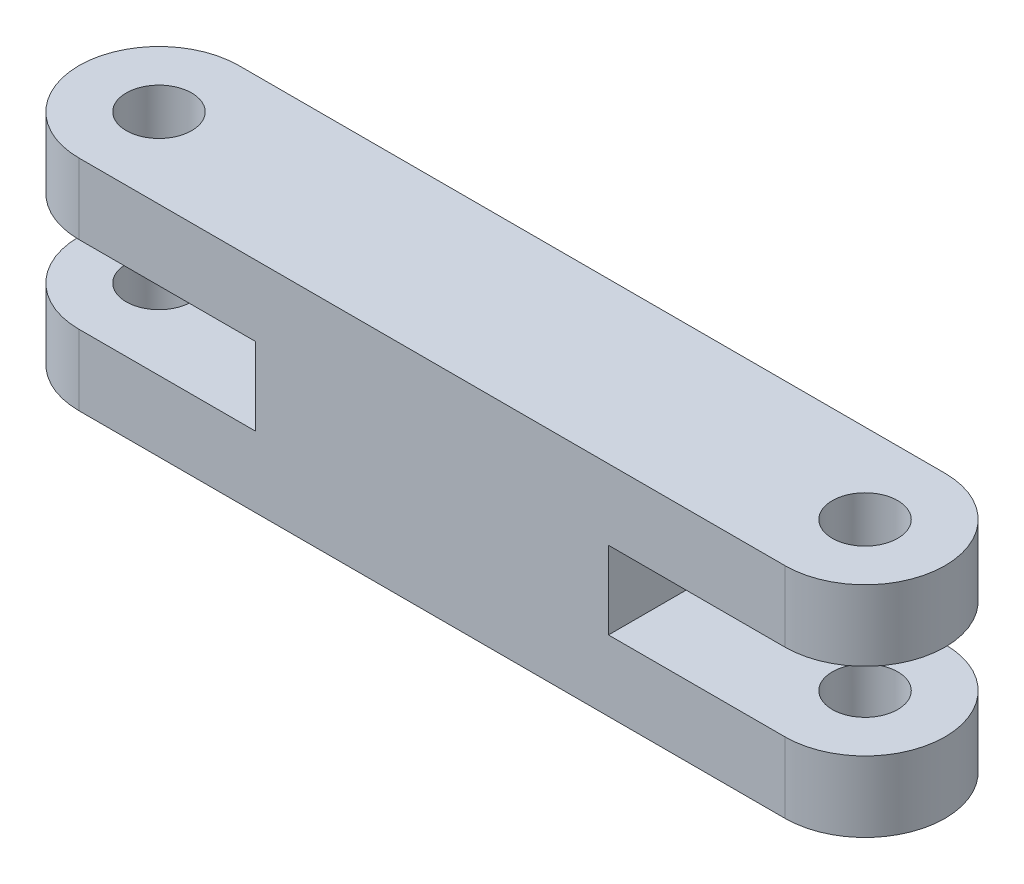
SolidWorks part; units mm, degrees
ref_plane "Front Plane" through (0, 0, 0) normal (0, 0, 1) x (1, 0, 0)
ref_plane "Top Plane" through (0, 0, 0) normal (0, 1, 0) x (1, 0, 0)
ref_plane "Right Plane" through (0, 0, 0) normal (1, 0, 0) x (0, 0, -1)
sketch "Sketch1" plane through (0, 0, 0) normal (0, 0, 1) x (1, 0, 0)
  line L0 (3.4, -9.3) -> (3.4, 0)
  line L1 (3.4, 0) -> (33.4, 0)
  line L2 (33.4, 0) -> (33.4, -9.3)
  line L3 (33.4, -9.3) -> (3.4, -9.3)
  point P2 (0, 0)
extrude "Boss-Extrude2" add sketch "Sketch1" along normal blind 3.4 and the other way blind 3.4
sketch "Sketch3" plane through (0, 0, 3.4) normal (0, 0, 1) x (1, 0, 0)
  line L0 (3.4, -3) -> (3.4, -6.3)
  line L1 (3.4, -3) -> (10.9, -3)
  line L2 (3.4, -6.3) -> (10.9, -6.3)
  line L3 (10.9, -3) -> (10.9, -6.3)
extrude "Cut-Extrude1" cut sketch "Sketch3" against normal blind 6.8 contours L0 L2 L3 L1
sketch "Sketch4" plane through (0, 0, 3.4) normal (0, 0, 1) x (1, 0, 0)
  line L0 (33.4, -3) -> (33.4, -6.3)
  line L1 (33.4, -3) -> (25.9, -3)
  line L2 (33.4, -6.3) -> (25.9, -6.3)
  line L3 (25.9, -3) -> (25.9, -6.3)
extrude "Cut-Extrude2" cut sketch "Sketch4" against normal blind 6.8 contours L0 L2 L3 L1
sketch "Sketch5" plane through (0, 0, 0) normal (0, 1, 0) x (1, 0, 0)
  line L0 (3.4, 3.4) -> (3.4, -3.4)
  arc A0 (3.4, 3.4) -> (3.4, -3.4) centre (3.4, 0) ccw
extrude "Boss-Extrude3" add sketch "Sketch5" against normal up to vertex (3 mm away) up to point (3.4, -3, -3.4)
sketch "Sketch6" plane through (0, 0, 0) normal (0, 1, 0) x (1, 0, 0)
  line L0 (33.4, 3.4) -> (33.4, -3.4)
  arc A0 (33.4, 3.4) -> (33.4, -3.4) centre (33.4, 0) cw
extrude "Boss-Extrude4" add sketch "Sketch6" against normal up to vertex (3 mm away) up to point (33.4, -3, -3.4)
sketch "Sketch7" plane through (0, -9.3, 0) normal (0, -1, 0) x (-1, 0, 0)
  line L0 (-3.4, -3.4) -> (-3.4, 3.4)
  arc A0 (-3.4, -3.4) -> (-3.4, 3.4) centre (-3.4, 0) ccw
extrude "Boss-Extrude5" add sketch "Sketch7" against normal up to vertex (3 mm away) up to point (3.4, -6.3, 3.4)
sketch "Sketch8" plane through (0, -9.3, 0) normal (0, -1, 0) x (-1, 0, 0)
  line L0 (-33.4, -3.4) -> (-33.4, 3.4)
  arc A0 (-33.4, -3.4) -> (-33.4, 3.4) centre (-33.4, 0) cw
extrude "Boss-Extrude6" add sketch "Sketch8" against normal up to vertex (3 mm away) up to point (33.4, -6.3, -3.4)
sketch "Sketch9" plane through (0, 0, 0) normal (0, 1, 0) x (1, 0, 0)
  circle A0 centre (3.4, 0) radius 1.39
extrude "Cut-Extrude3" cut sketch "Sketch9" against normal up to vertex (9.3 mm away) up to point (3.4, -9.3, 3.4)
sketch "Sketch10" plane through (0, 0, 0) normal (0, 1, 0) x (1, 0, 0)
  circle A0 centre (33.4, 0) radius 1.39
extrude "Cut-Extrude4" cut sketch "Sketch10" against normal up to vertex (9.3 mm away) up to point (33.4, -9.3, -3.4)
